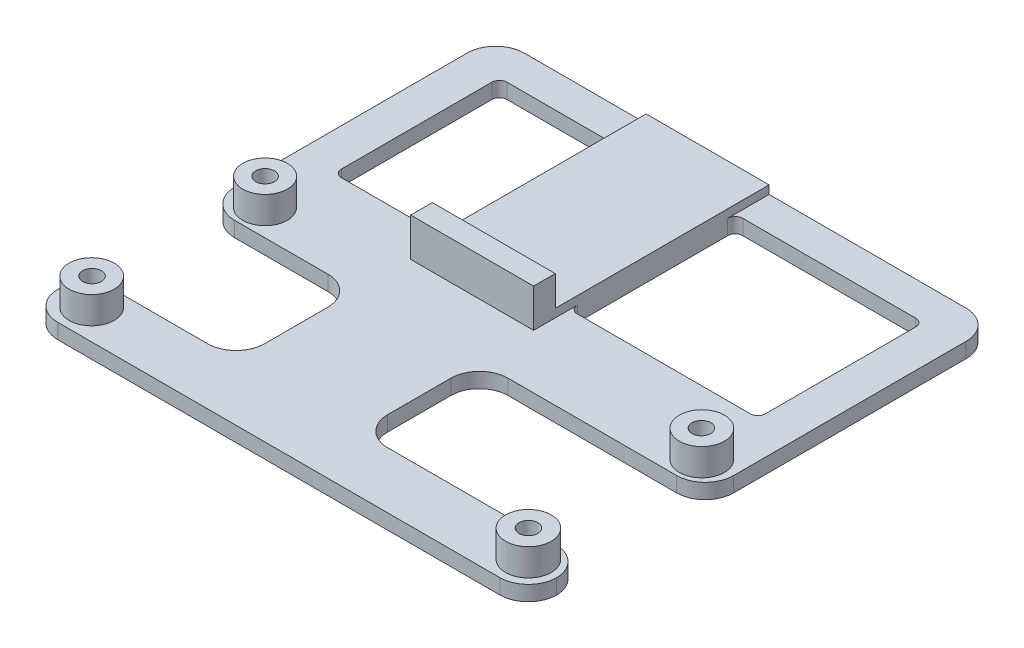
SolidWorks part; units mm, degrees
ref_plane "前视基准面" through (0, 0, 0) normal (0, 0, 1) x (1, 0, 0)
ref_plane "上视基准面" through (0, 0, 0) normal (0, 1, 0) x (1, 0, 0)
ref_plane "右视基准面" through (0, 0, 0) normal (1, 0, 0) x (0, 0, -1)
other "Configuration Table"
sketch "草图1" plane through (0, 0, 0) normal (0, 1, 0) x (1, 0, 0)
  line L1 (-33.135, 46.435) -> (33.2082, 46.435)
  line L2 (-33.135, 46.435) -> (-33.135, -16.565)
  line L3 (-33.135, -16.565) -> (33.2082, -16.565)
  line L4 (33.2082, 46.435) -> (33.2082, -16.565)
  point P6 (0, 0)
  point P9 (0, 0)
  point P10 (0, 0)
  dimension "D1" = 63
  dimension "D2" = 66.3431
extrude "凸台-拉伸1" add sketch "草图1" along normal blind 2
sketch "草图2" plane through (0, 2, 0) normal (0, 1, 0) x (1, 0, 0)
  circle A0 centre (29.2416, 10.96) radius 3
  circle A1 centre (29.2166, -12.065) radius 3.0354
  circle A2 centre (-28.7834, 10.935) radius 2.9646
  circle A3 centre (-28.8084, -12.09) radius 3
extrude "凸台-拉伸2" add sketch "草图2" along normal blind 3.6
sketch "草图6" plane through (0, 2, 0) normal (0, 1, 0) x (1, 0, 0)
  line L0 (33.2082, -16.565) -> (33.2082, 46.435) construction
  line L1 (33.2082, 7.435) -> (3.2082, 7.435)
  line L2 (33.2082, 7.435) -> (33.2082, -8.565)
  line L3 (33.2082, -8.565) -> (3.2082, -8.565)
  line L4 (3.2082, 7.435) -> (3.2082, -8.565)
  line L5 (-33.135, 46.435) -> (-33.135, -16.565) construction
  line L6 (-33.135, 7.435) -> (-13.135, 7.435)
  line L7 (-33.135, 7.435) -> (-33.135, -8.565)
  line L8 (-33.135, -8.565) -> (-13.135, -8.565)
  line L9 (-13.135, 7.435) -> (-13.135, -8.565)
  line L10 (-33.135, -16.565) -> (33.2082, -16.565) construction
  line L12 (-28.135, 41.435) -> (-13.135, 41.435)
  line L13 (-28.135, 41.435) -> (-28.135, 19.435)
  line L14 (-28.135, 19.435) -> (-13.135, 19.435)
  line L15 (-13.135, 41.435) -> (-13.135, 19.435)
  line L17 (28.2082, 41.435) -> (3.2082, 41.435)
  line L18 (28.2082, 41.435) -> (28.2082, 19.435)
  line L19 (28.2082, 19.435) -> (3.2082, 19.435)
  line L20 (3.2082, 41.435) -> (3.2082, 19.435)
  line L21 (33.2082, 46.435) -> (-33.135, 46.435) construction
  line L22 (-33.135, 46.435) -> (-33.135, -16.565) construction
  line L23 (33.2082, -16.565) -> (33.2082, 46.435) construction
  line L24 (33.1254, -16.065) -> (34.8366, -16.065) construction
  line L25 (-33.135, -16.565) -> (33.2082, -16.565)
  line L26 (-33.135, -16.565) -> (-33.135, -16.065)
  line L27 (-33.135, -16.065) -> (33.2082, -16.065)
  line L28 (33.2082, -16.565) -> (33.2082, -16.065)
  line L30 (33.2082, 46.435) -> (-33.135, 46.435)
  line L31 (33.2082, 46.435) -> (33.2082, 45.935)
  line L32 (33.2082, 45.935) -> (-33.135, 45.935)
  line L33 (-33.135, 46.435) -> (-33.135, 45.935)
  dimension "D1" = 16
  dimension "D2" = 8
  dimension "D3" = 20
  dimension "D4" = 30
  dimension "D5" = 5
  dimension "D6" = 22
  dimension "D7" = 5
  dimension "D8" = 5
  dimension "D9" = 0.5
extrude "切除-拉伸1" cut sketch "草图6" against normal through all
fillet "圆角1" radius 3.8 12 edges at (33.2082, 1, -7.435) (33.2082, 1, 8.565) (3.2082, 1, 8.565) (3.2082, 1, -7.435) (-13.135, 1, 8.565) (-13.135, 1, -7.435) (-33.135, 1, 8.565) (-33.135, 1, -7.435) (-33.135, 1, 16.065) (33.2082, 1, 16.065) (33.2082, 1, -45.935) (-33.135, 1, -45.935)
sketch "草图3" plane through (0, 2, 0) normal (0, 1, 0) x (1, 0, 0)
  line L1 (-13.135, 45.935) -> (3.2082, 45.935)
  line L2 (-13.135, 45.935) -> (-13.135, 14.635)
  line L3 (-13.135, 14.635) -> (3.2082, 14.635)
  line L4 (3.2082, 45.935) -> (3.2082, 14.635)
  line L11 (-13.135, -4.765) -> (-13.135, 3.635) construction
  line L12 (3.2082, 3.635) -> (3.2082, -4.765) construction
  line L13 (-29.335, 45.935) -> (29.4082, 45.935) construction
  point P4 (-13.135, 45.9525)
  point P5 (-13.135, 45.935)
  point P6 (0, 0)
  point P7 (0, 0)
  point P12 (0, 0)
  point P13 (0, 0)
  point P14 (0, 0)
extrude "凸台-拉伸3" add sketch "草图3" along normal blind 1.1
sketch "草图5" plane through (0, 3.1, 0) normal (0, 1, 0) x (1, 0, 0)
  line L0 (-13.135, 45.935) -> (-13.135, 14.635) construction
  line L1 (3.2082, 14.635) -> (-13.135, 14.635)
  line L2 (3.2082, 14.635) -> (3.2082, 17.5144)
  line L3 (3.2082, 17.5144) -> (-13.135, 17.5144)
  line L4 (-13.135, 14.635) -> (-13.135, 17.5144)
  point P14 (0, 0)
  dimension "D1" = 2.8794
extrude "凸台-拉伸4" add sketch "草图5" along normal blind 4
fillet "圆角2" radius 1 8 edges at (3.2082, 1, -19.435) (-28.135, 1, -19.435) (-13.135, 1, -19.435) (-13.135, 1, -41.435) (-28.135, 1, -41.435) (3.2082, 1, -41.435) (28.2082, 1, -19.435) (28.2082, 1, -41.435)
sketch "草图7" plane through (0, 5.6, 0) normal (0, 1, 0) x (1, 0, 0)
  circle A0 centre (-28.7834, 10.935) radius 1.25
  circle A1 centre (29.2166, 10.935) radius 1.25
  circle A2 centre (29.2166, -12.065) radius 1.25
  circle A3 centre (-28.7834, -12.065) radius 1.25
extrude "切除-拉伸2" cut sketch "草图7" against normal blind 4 draft 2
